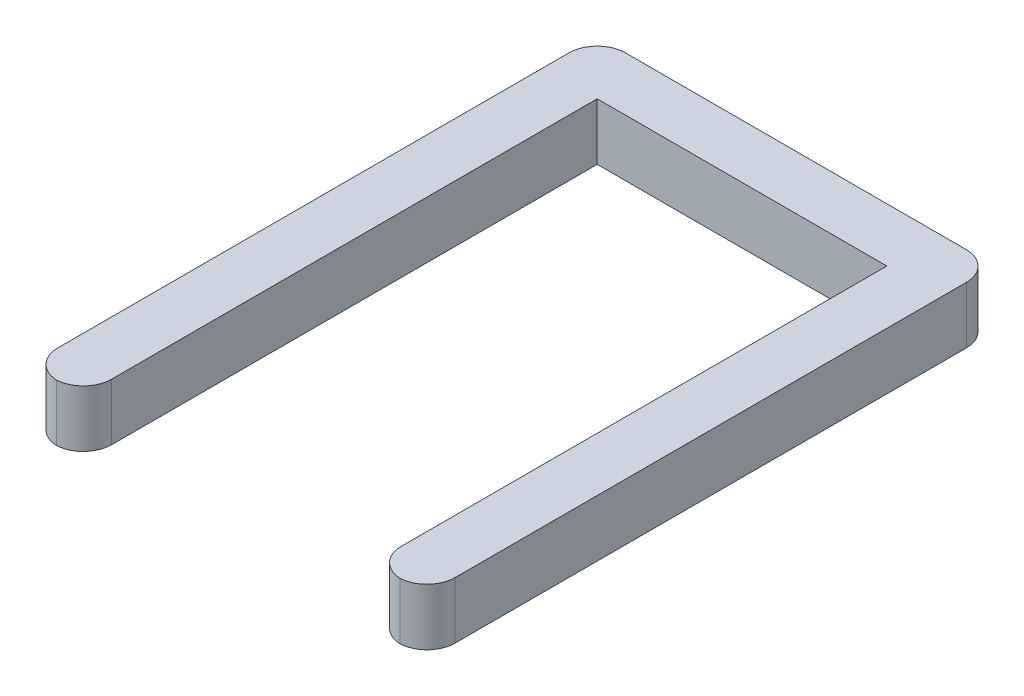
SolidWorks part; units mm, degrees
ref_plane "Alzado" through (0, 0, 0) normal (0, 0, 1) x (1, 0, 0)
ref_plane "Planta" through (0, 0, 0) normal (0, 1, 0) x (1, 0, 0)
ref_plane "Vista lateral" through (0, 0, 0) normal (1, 0, 0) x (0, 0, -1)
sketch "Croquis1" plane through (0, 0, 0) normal (0, 1, 0) x (1, 0, 0)
  line L1 (0, 0) -> (70, 0)
  line L2 (0, 0) -> (0, -100)
  line L3 (0, -100) -> (70, -100)
  line L4 (70, 0) -> (70, -100)
  dimension "D1" = 70
  dimension "D2" = 100
extrude "Saliente-Extruir1" add sketch "Croquis1" along normal blind 10
sketch "Croquis2" plane through (0, 10, 0) normal (0, 1, 0) x (1, 0, 0)
  line L0 (0, -100) -> (70, -100) construction
  line L1 (9.5, -9.5) -> (60.5, -9.5)
  line L2 (9.5, -9.5) -> (9.5, -100)
  line L3 (9.5, -100) -> (60.5, -100)
  line L4 (60.5, -9.5) -> (60.5, -100)
  line L5 (0, 0) -> (0, -100) construction
  line L7 (70, 0) -> (0, 0) construction
  dimension "D1" = 51
  dimension "D2" = 9.5
  dimension "D3" = 9.5
extrude "Cortar-Extruir1" cut sketch "Croquis2" against normal blind 10
fillet "Redondeo1" radius 5 6 edges at (9.5, 5, 100) (60.5, 5, 100) (0, 5, 0) (0, 5, 100) (70, 5, 100) (70, 5, 0)
